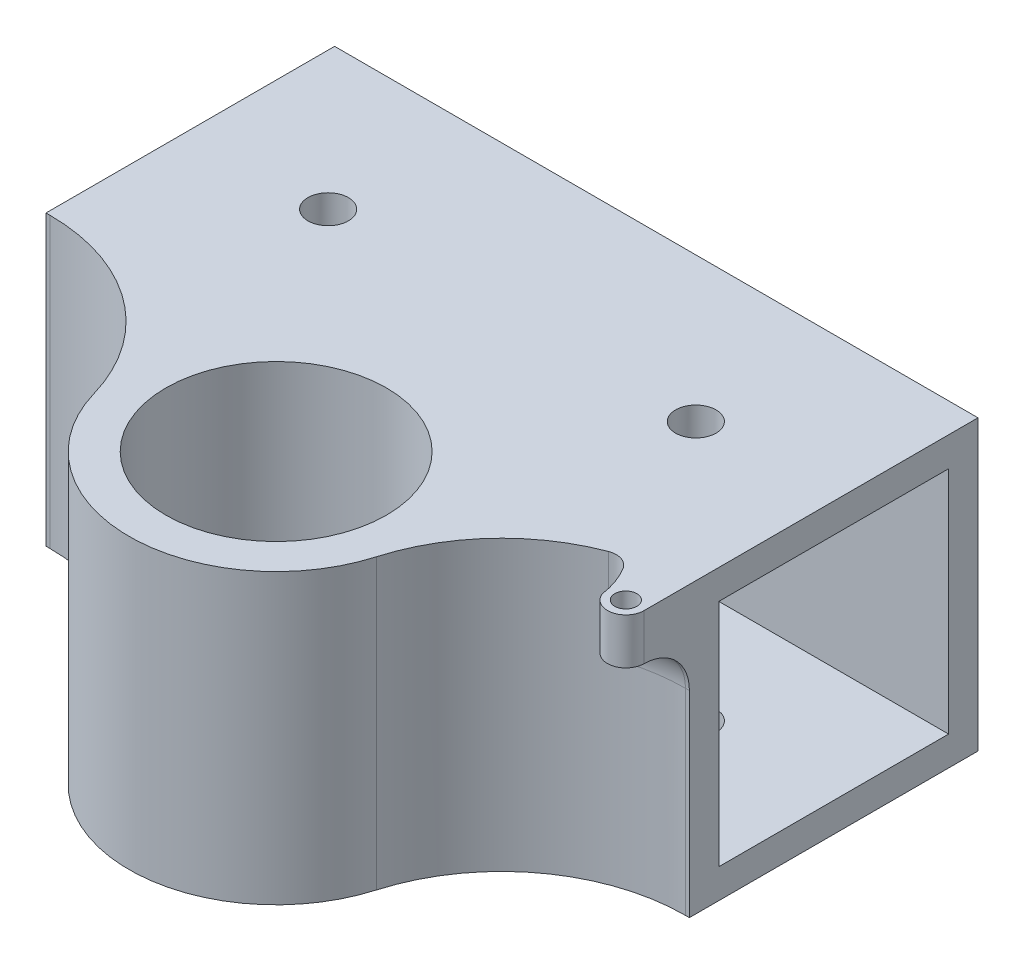
SolidWorks part; units mm, degrees
ref_plane "Front" through (0, 0, 0) normal (0, 0, 1) x (1, 0, 0)
ref_plane "Top" through (0, 0, 0) normal (0, 1, 0) x (1, 0, 0)
ref_plane "Right" through (0, 0, 0) normal (1, 0, 0) x (0, 0, -1)
sketch "Эскиз1" plane through (0, 0, 0) normal (1, 0, 0) x (0, 0, -1)
  line L1 (-12.5, -12.5) -> (12.5, -12.5)
  line L2 (-12.5, -12.5) -> (-12.5, 12.5)
  line L3 (-12.5, 12.5) -> (12.5, 12.5)
  line L4 (12.5, -12.5) -> (12.5, 12.5)
  line L5 (-12.5, -12.5) -> (12.5, 12.5) construction
  line L6 (-12.5, 12.5) -> (12.5, -12.5) construction
  point P0 (0, 0)
  dimension "D1" = 25
  dimension "D2" = 25
extrude "Вытянуть-Тонкостенный1" add sketch "Эскиз1" along normal blind 70 thin thin type one direction wall 3.2
sketch "Эскиз3" plane through (0, 15.7, 0) normal (0, 1, 0) x (1, 0, 0)
  line L0 (0, 0) -> (70, 0) construction
  line L1 (70, 15.7) -> (70, -15.7) construction
  line L2 (35, 0) -> (35, -32.0332) construction
  circle A0 centre (35, -25.6592) radius 16
  circle A1 centre (35, -25.6592) radius 6
extrude "Бобышка-Вытянуть1" add sketch "Эскиз3" against normal up to surface (31.4 mm away) up to face at (35, -15.7, 0)
sketch "Эскиз4" plane through (0, 0, 0) normal (-1, 0, 0) x (0, 0, 1)
  line L1 (12.5, -12.5) -> (-12.5, -12.5)
  line L2 (12.5, -12.5) -> (12.5, 12.5)
  line L3 (12.5, 12.5) -> (-12.5, 12.5)
  line L4 (-12.5, -12.5) -> (-12.5, 12.5)
extrude "Вырез-Вытянуть1" cut sketch "Эскиз4" against normal through all
sketch "Эскиз5" plane through (0, -15.7, 0) normal (0, -1, 0) x (1, 0, 0)
  circle A0 centre (35, 25.6592) radius 12
extrude "Вырез-Вытянуть2" cut sketch "Эскиз5" against normal blind 4
sketch "Эскиз6" plane through (0, -11.7, 0) normal (0, -1, 0) x (1, 0, 0)
  circle A0 centre (35, 25.6592) radius 8 construction
  circle A1 centre (35, 33.6592) radius 1.5
  circle A2 centre (27, 25.6592) radius 1.5
  circle A3 centre (43, 25.6592) radius 1.5
  circle A4 centre (35, 17.6592) radius 1.5
extrude "Вырез-Вытянуть3" cut sketch "Эскиз6" against normal through all
fillet "Скругление1" radius 20 2 edges at (47.5225, 0, 15.7) (22.4775, 0, 15.7)
sketch "Эскиз7" plane through (0, 15.7, 0) normal (0, 1, 0) x (1, 0, 0)
  circle A0 centre (35, -25.6592) radius 12
extrude "Вырез-Вытянуть4" cut sketch "Эскиз7" against normal blind 20
sketch "Эскиз8" plane through (0, 15.7, 0) normal (0, 1, 0) x (1, 0, 0)
  line L0 (0, 0) -> (70, 0) construction
  line L1 (70, 15.7) -> (70, -15.7) construction
  line L2 (0, 15.7) -> (0, -15.7) construction
  circle A0 centre (15, 0) radius 2.2
  circle A1 centre (55, 0) radius 2.2
  dimension "D1" = 15
  dimension "D2" = 15
extrude "Вырез-Вытянуть5" cut sketch "Эскиз8" against normal through all
sketch "Эскиз9" plane through (0, 15.7, 0) normal (0, -1, 0) x (1, 0, 0)
  line L0 (70, 15.7) -> (70, 20.6235)
  circle A0 centre (68.0094, 20.6235) radius 1.2
  arc A1 (70, 20.6235) -> (66.1427, 21.3149) centre (68.0094, 20.6235) ccw
  arc A2 (66.1427, 21.3149) -> (63.9425, 16.5085) centre (56.9875, 22.599) cw
  arc A6 (50.3651, 30.1218) -> (69.5714, 15.7) centre (69.5714, 35.7) ccw construction
  arc A7 (63.9425, 16.5085) -> (70, 15.7) centre (69.5992, 35.7949) ccw
  point P5 (68.0451, 20.9043)
  point P9 (68.0094, 20.6235)
  point P10 (68.0665, 21.2177)
  point P13 (66.0188, 20.6235)
extrude "Бобышка-Вытянуть4" add sketch "Эскиз9" along normal blind 5
fillet "Скругление2" radius 5 2 edges at (69.7857, 10.7, 15.7) (66.7281, 10.7, 15.9031)
fillet "Скругление3" radius 2 1 edges at (63.9425, 10.7, 16.5085)
